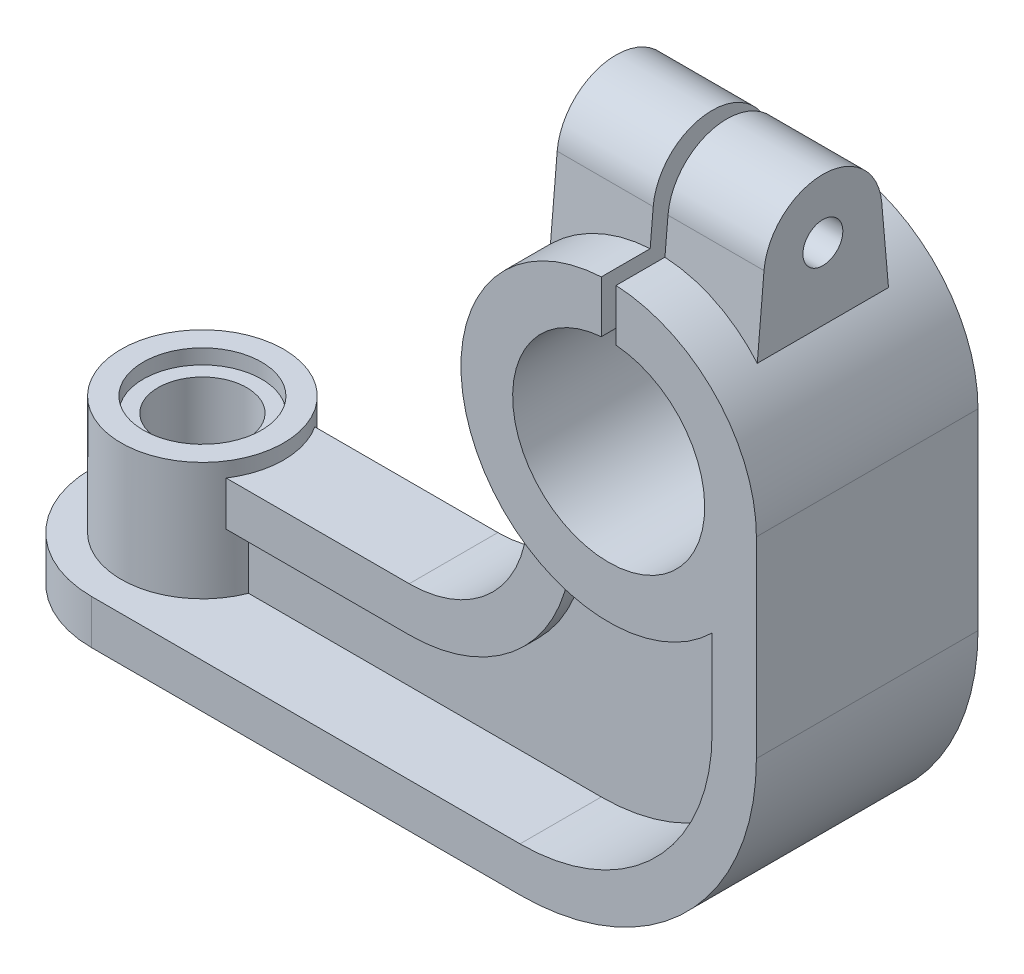
SolidWorks part; units mm, degrees
material "ASTM A36 Steel"
ref_plane "Front Plane" through (0, 0, 0) normal (0, 0, 1) x (1, 0, 0)
ref_plane "Top Plane" through (0, 0, 0) normal (0, 1, 0) x (1, 0, 0)
ref_plane "Right Plane" through (0, 0, 0) normal (1, 0, 0) x (0, 0, -1)
sketch "Sketch1" plane through (0, 0, 0) normal (0, 0, 1) x (1, 0, 0)
  line L0 (50, 145) -> (50, 80)
  line L1 (-30, 0) -> (-175, 0)
  line L2 (-175, 0) -> (-175, 50)
  line L3 (-175, 50) -> (-90, 50)
  line L4 (-50, 90) -> (-50, 145)
  line L5 (-50, 145) -> (50, 145)
  circle A0 centre (0, 145) radius 50
  arc A1 (50, 80) -> (-30, 0) centre (-30, 80) cw
  arc A2 (-90, 50) -> (-50, 90) centre (-90, 90) ccw
  point P11 (50, 0)
  dimension "D1" = 100
  dimension "D5" = 80
  dimension "D6" = 40
  dimension "D2" = 145
  dimension "D3" = 175
  dimension "D4" = 50
extrude "Boss-Extrude1" add sketch "Sketch1" along normal mid plane 20 contours A2 L4 L5 L0 A1 L1 L2 L3
extrude "Boss-Extrude2" add sketch "Sketch1<3>" along normal mid plane 75 contours A0
sketch "Sketch1<3>" plane through (0, 0, 0) normal (0, 0, 1) x (1, 0, 0) same geometry as "Sketch1"
sketch "Sketch2" plane through (0, 0, 0) normal (0, 0, 1) x (1, 0, 0)
  line L14 (-35, 90) -> (-35, 145)
  line L15 (-175, 35) -> (-90, 35)
  line L16 (-35, 90) -> (-35, 145)
  line L17 (-175, 35) -> (-90, 35)
  line L19 (-30, 15) -> (-175, 15)
  line L20 (-30, 15) -> (-175, 15)
  line L21 (-50, 90) -> (-50, 145) construction
  line L22 (35, 145) -> (35, 80)
  line L23 (35, 145) -> (35, 80)
  line L24 (-175, 50) -> (-90, 50) construction
  line L25 (-50, 90) -> (-50, 145)
  line L26 (-175, 50) -> (-90, 50)
  line L27 (50, 145) -> (50, 80) construction
  line L28 (-30, 0) -> (-175, 0) construction
  line L29 (50, 145) -> (50, 80)
  line L30 (-30, 0) -> (-175, 0)
  line L31 (-175, 0) -> (-175, 15)
  line L32 (-175, 35) -> (-175, 50)
  line L33 (-50, 145) -> (-35, 145)
  line L34 (35, 145) -> (50, 145)
  arc A6 (-90, 35) -> (-35, 90) centre (-90, 90) ccw
  arc A7 (-90, 35) -> (-35, 90) centre (-90, 90) ccw
  arc A8 (-90, 50) -> (-50, 90) centre (-90, 90) ccw construction
  arc A9 (-30, 15) -> (35, 80) centre (-30, 80) ccw
  arc A10 (-30, 15) -> (35, 80) centre (-30, 80) ccw
  arc A11 (-90, 50) -> (-50, 90) centre (-90, 90) ccw
  arc A12 (-30, 0) -> (50, 80) centre (-30, 80) ccw construction
  arc A13 (-30, 0) -> (50, 80) centre (-30, 80) ccw
  dimension "D1" = 15
  dimension "D2" = 15
  dimension "D3" = 15
extrude "Boss-Extrude3" add sketch "Sketch2" along normal mid plane 30 contours A11 L26 L32 L17 A7 L16 L33 L25 region at (-52.3681, 52.3681, 0)
extrude "Boss-Extrude4" add sketch "Sketch2<3>" along normal mid plane 75 contours A13 L29 L34 L23 A10 L20 L31 L30
sketch "Sketch2<3>" plane through (0, 0, 0) normal (0, 0, 1) x (1, 0, 0) same geometry as "Sketch2"
sketch "Sketch4" plane through (0, 0, 0) normal (0, 0, 1) x (1, 0, 0)
  line L0 (-175, 0) -> (-175, 55) construction
  line L1 (-175, 55) -> (-202.5, 55)
  line L2 (-202.5, 55) -> (-202.5, 15)
  line L3 (-202.5, 15) -> (-212.5, 15)
  line L4 (-212.5, 15) -> (-212.5, 0)
  line L5 (-212.5, 0) -> (-175, 0)
  line L6 (-175, 0) -> (-175, 55)
  point P10 (-212.5, 12.562)
  dimension "D1" = 75
  dimension "D2" = 55
  dimension "D3" = 5
revolve "Revolve1" add sketch "Sketch4" angle 360 about L0
sketch "Sketch6" plane through (0, 0, 0) normal (1, 0, 0) x (0, 0, -1)
  line L0 (-25.3257, 145) -> (25.3257, 145)
  line L1 (25.3257, 145) -> (19.9239, 206.7431)
  line L2 (-19.9239, 206.7431) -> (-25.3257, 145)
  line L3 (0, 174.78) -> (0, 211.7829) construction
  line L4 (-37.5, 145) -> (37.5, 145) construction
  arc A0 (19.9239, 206.7431) -> (-19.9239, 206.7431) centre (0, 205) ccw
  dimension "D1" = 205
  dimension "D2" = 20
  dimension "D3" = 10
extrude "Boss-Extrude5" add sketch "Sketch6" along normal mid plane 70
hole_wizard "CBORE for M12 SBHCS1" positions "Sketch10" profile "Sketch11" counterbore size "M12" standard "ANSI Metric" end condition through all
sketch "Sketch10" plane through (-35, 0, 0) normal (-1, 0, 0) x (0, 0, 1)
  point P0 (0, 205)
sketch "Sketch11" plane through (-35, 205, 0) normal (0, 1, 0) x (0, 0, 1)
  line L0 (0, 0) -> (0, 85)
  line L1 (0, 85) -> (6.75, 85)
  line L3 (6.75, 85) -> (6.75, 6.6)
  line L4 (11, 6.6) -> (6.75, 6.6)
  line L5 (11, 6.6) -> (11, 0.025)
  line L6 (11, 0.025) -> (11.025, 0)
  line L7 (11.025, 0) -> (0, 0)
  line L8 (-11, 0.025) -> (-11.025, 0) construction
  line L11 (0, -6.35) -> (0, 107.95) construction
  dimension "Thru Hole Dia." = 13.5
  dimension "Thru Hole Depth" = 85
  dimension "C'Bore Dia." = 22
  dimension "C'Bore Depth" = 6.6
  dimension "Near C'Sink Dia." = 22.05
  dimension "Near C'Sink Angle" = 90
sketch "Sketch12" plane through (0, 0, 0) normal (0, 0, 1) x (1, 0, 0)
  line L0 (35, 225) -> (-35, 225) construction
  line L1 (-2.5, 130) -> (2.5, 130)
  line L2 (-2.5, 130) -> (-2.5, 225)
  line L3 (-2.5, 225) -> (2.5, 225)
  line L4 (2.5, 130) -> (2.5, 225)
  line L5 (-2.5, 130) -> (2.5, 225) construction
  line L6 (-2.5, 225) -> (2.5, 130) construction
  circle A0 centre (0, 145) radius 32.5
  point P3 (0, 177.5)
  dimension "D1" = 65
  dimension "D2" = 5
extrude "Cut-Extrude1" cut sketch "Sketch12" against normal through all both and the other way through all contours A0 | L3 L4 L1 L2
sketch "Sketch13" plane through (0, 0, 0) normal (0, 0, 1) x (1, 0, 0)
  line L0 (-175, 55) -> (-175, 0) construction
  line L1 (-147.5, 55) -> (-202.5, 55) construction
  line L2 (-175, 0) -> (-200, 0)
  line L3 (-212.5, 0) -> (-175, 0) construction
  line L4 (-200, 0) -> (-200, 5)
  line L5 (-200, 5) -> (-190, 5)
  line L6 (-190, 5) -> (-190, 50)
  line L7 (-190, 50) -> (-195, 50)
  line L8 (-195, 50) -> (-195, 55)
  line L9 (-195, 55) -> (-175, 55)
  line L10 (-175, 55) -> (-175, 0)
  dimension "D1" = 5
  dimension "D2" = 40
  dimension "D3" = 30
  dimension "D4" = 50
revolve "Cut-Revolve1" cut sketch "Sketch13" angle 360 about L0
